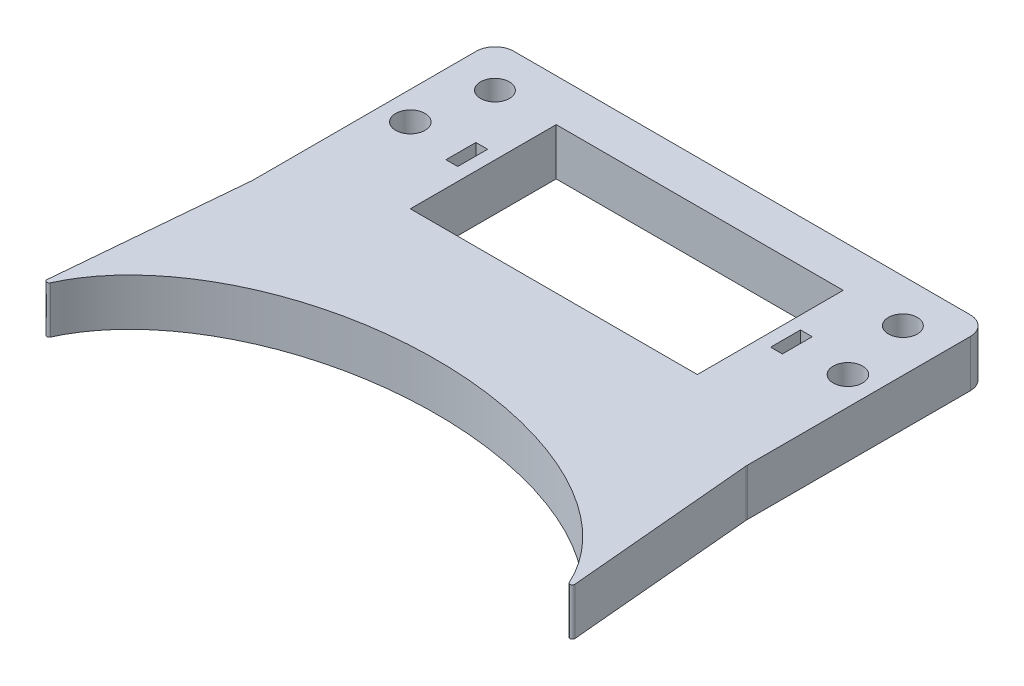
SolidWorks part; units mm, degrees
ref_plane "Front Plane" through (0, 0, 0) normal (0, 0, 1) x (1, 0, 0)
ref_plane "Top Plane" through (0, 0, 0) normal (0, 1, 0) x (1, 0, 0)
ref_plane "Right Plane" through (0, 0, 0) normal (1, 0, 0) x (0, 0, -1)
sketch "Sketch1" plane through (0, 0, 0) normal (0, 1, 0) x (1, 0, 0)
  line L1 (-52.5, -32.5) -> (52.5, -32.5)
  line L2 (-52.5, -32.5) -> (-52.5, 32.5)
  line L3 (-52.5, 32.5) -> (52.5, 32.5)
  line L4 (52.5, -32.5) -> (52.5, 32.5)
  line L5 (0, 32.5) -> (0, -32.5) construction
  line L6 (-52.5, 0) -> (52.5, 0) construction
  point P0 (0, 0)
  dimension "D1" = 105
  dimension "D2" = 65
extrude "Boss-Extrude1" add sketch "Sketch1" along normal blind 10
sketch "Sketch2" plane through (0, 10, 0) normal (0, 1, 0) x (1, 0, 0)
  line L6 (-30.5, 23.5) -> (30.5, 23.5)
  line L7 (-30.5, 23.5) -> (-30.5, -7.5)
  line L8 (-30.5, -7.5) -> (30.5, -7.5)
  line L9 (30.5, 23.5) -> (30.5, -7.5)
  line L10 (0, -7.5) -> (0, 23.5) construction
  line L11 (-30.5, 8) -> (30.5, 8) construction
  line L12 (0, 0) -> (0, -7.5) construction
  line L14 (-52.5, -32.5) -> (52.5, -32.5) construction
  point P0 (0, 8)
  dimension "D1" = 31
  dimension "D2" = 61
  dimension "D3" = 25
extrude "Cut-Extrude1" cut sketch "Sketch2" against normal through all
sketch "Sketch4" plane through (0, 10, 0) normal (0, 1, 0) x (1, 0, 0)
  line L2 (-46.5, 8.5) -> (-34.5, 8.5) construction
  line L3 (30.5, 23.5) -> (-30.5, 23.5) construction
  line L4 (-33.25, 11.675) -> (-35.75, 11.675)
  line L5 (-33.25, 11.675) -> (-33.25, 5.325)
  line L6 (-33.25, 5.325) -> (-35.75, 5.325)
  line L7 (-35.75, 11.675) -> (-35.75, 5.325)
  line L8 (-34.5, 5.325) -> (-34.5, 11.675) construction
  line L9 (-33.25, 8.5) -> (-35.75, 8.5) construction
  line L10 (-30.5, 23.5) -> (-30.5, -7.5) construction
  circle A0 centre (-46.5, 8.5) radius 3.125
  dimension "D1" = 6.25
  dimension "D2" = 15
  dimension "D3" = 16
  dimension "D4" = 2.5
  dimension "D5" = 6.35
  dimension "D6" = 2.75
extrude "Cut-Extrude3" cut sketch "Sketch4" against normal through all
sketch "Sketch5" plane through (0, 0, 0) normal (0, 1, 0) x (1, 0, 0)
  line L0 (0, 0) -> (0, -70) construction
  line L1 (-52.5, -32.5) -> (52.5, -32.5) construction
  line L2 (-52.5, -19.0391) -> (-56.4081, -62.7266)
  line L3 (-52.5, 32.5) -> (-52.5, -32.5) construction
  line L4 (-52.5, -19.0391) -> (0, -32.5)
  ellipse E0 centre (0, -70) end of major axis (-57.5, -70) minor radius 37.5
  dimension "D1" = 115
  dimension "D2" = 70
extrude "Boss-Extrude2" add sketch "Sketch5" along normal up to surface (10 mm away) contours E0 L4 L2 region at (-39.0021, 0, 34.1841) up to face at (-46.5, 10, -5.375)
sketch "Sketch6" plane through (0, 10, 0) normal (0, 1, 0) x (1, 0, 0)
  circle A0 centre (-43.3477, 23.3308) radius 3.075
  dimension "D1" = 6.15
extrude "Cut-Extrude4" cut sketch "Sketch6" against normal through all
mirror "Mirror1" about plane through (0, 0, 0) normal (1, 0, 0) of "Cut-Extrude4", "Boss-Extrude2", "Cut-Extrude3"
fillet "Fillet1" radius 4 4 edges at (-52.5, 5, 19.0391) (52.5, 5, 19.0391) (52.5, 5, -32.5) (-52.5, 5, -32.5)
fillet "Fillet2" radius 0.5 2 edges at (56.4081, 5, 62.7266) (-56.4081, 5, 62.7266)
